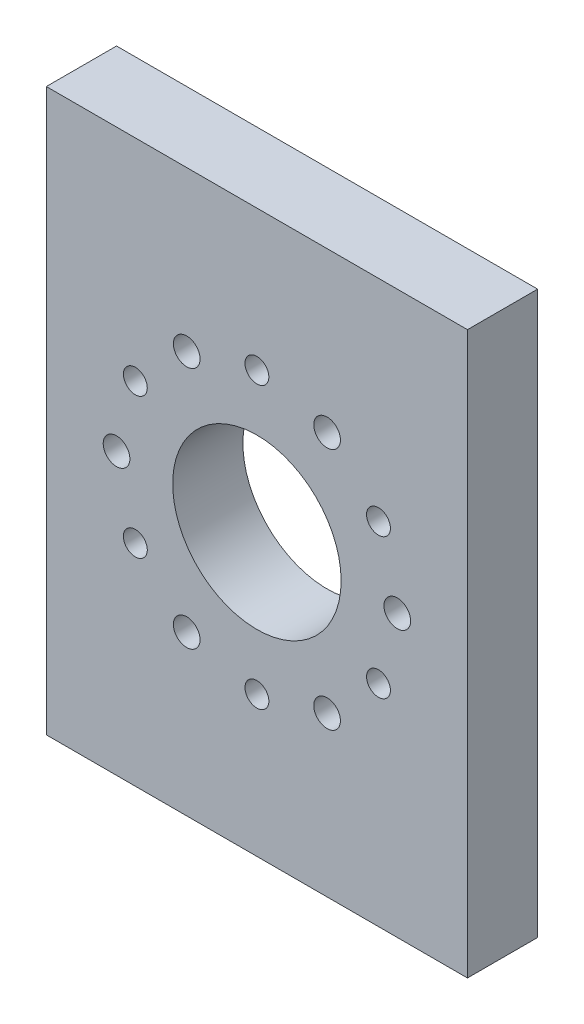
SolidWorks part; units mm, degrees
ref_plane "Front Plane" through (0, 0, 0) normal (0, 0, 1) x (1, 0, 0)
ref_plane "Top Plane" through (0, 0, 0) normal (0, 1, 0) x (1, 0, 0)
ref_plane "Right Plane" through (0, 0, 0) normal (1, 0, 0) x (0, 0, -1)
sketch "Sketch1" plane through (0, 0, 0) normal (0, 0, 1) x (1, 0, 0)
  line L1 (-38.1, -50.8) -> (38.1, -50.8)
  line L2 (-38.1, -50.8) -> (-38.1, 50.8)
  line L3 (-38.1, 50.8) -> (38.1, 50.8)
  line L4 (38.1, -50.8) -> (38.1, 50.8)
  line L5 (-38.1, -50.8) -> (38.1, 50.8) construction
  line L6 (-38.1, 50.8) -> (38.1, -50.8) construction
  circle A0 centre (0, 0) radius 15.24
  point P0 (0, 0)
  dimension "D1" = 76.2
  dimension "D2" = 101.6
extrude "Boss-Extrude1" add sketch "Sketch1" along normal blind 12.7
sketch "Sketch2" plane through (0, 0, 12.7) normal (0, 0, 1) x (1, 0, 0)
  circle A0 centre (0, 0) radius 25.4 construction
  circle A2 centre (-25.4, 0) radius 2.413
  circle A3 centre (0, -25.4) radius 2.159
  dimension "D1" = 4.318
  dimension "D2" = 4.826
  dimension "D3" = 50.8
extrude "Initial Mounting" cut sketch "Sketch2" against normal through all
pattern_circular "Mounting Pattern" count 6 over 360 about axis through (0, 0, 12.7) along (0, 0, 1) of "Initial Mounting"
